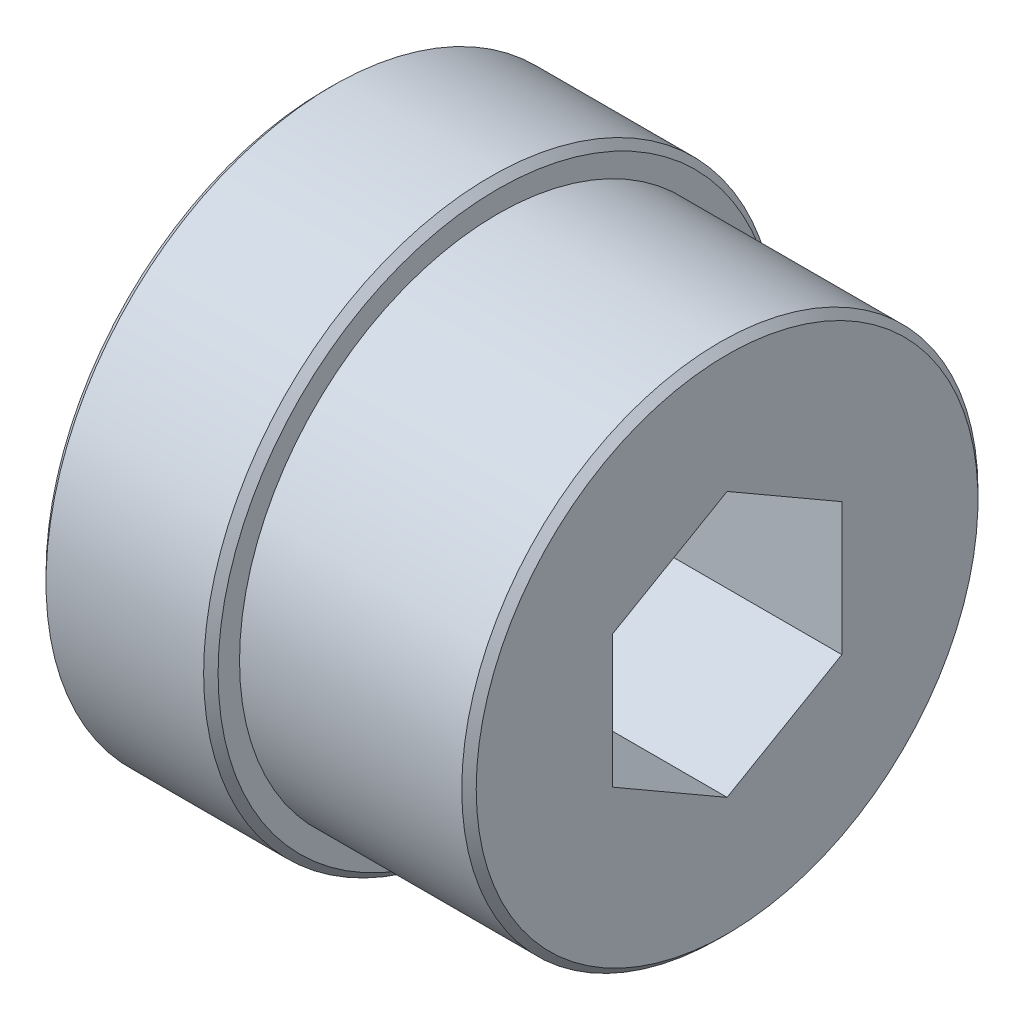
SolidWorks part; units mm, degrees
material "Nylon 101"
ref_plane "Front Plane" through (0, 0, 0) normal (0, 0, 1) x (1, 0, 0)
ref_plane "Top Plane" through (0, 0, 0) normal (0, 1, 0) x (1, 0, 0)
ref_plane "Right Plane" through (0, 0, 0) normal (1, 0, 0) x (0, 0, -1)
sketch "Sketch1" plane through (0, 0, 0) normal (1, 0, 0) x (0, 0, -1)
  circle A0 centre (0, 0) radius 14.2875
  dimension "D1" = 28.575
extrude "Boss-Extrude1" add sketch "Sketch1" along normal blind 12.7
sketch "Sketch2" plane through (0, 0, 0) normal (-1, 0, 0) x (0, 0, 1)
  circle A0 centre (0, 0) radius 15.875
  dimension "D1" = 31.75
extrude "Boss-Extrude2" add sketch "Sketch2" along normal blind 9.525
sketch "Sketch3" plane through (-9.525, 0, 0) normal (-1, 0, 0) x (0, 0, 1)
  circle A0 centre (0, 0) radius 11.1125
  dimension "D1" = 22.225
chamfer "Chamfer1" distance 0.4 angle 45 3 edges at (12.7, 0, -14.2875) (-9.525, 0, 15.875) (0, 0, 15.875)
sketch "Sketch4" plane through (-9.525, 0, 0) normal (-1, 0, 0) x (0, 0, 1)
  line L1 (0, 7.3323) -> (-6.35, 3.6662)
  line L2 (-6.35, 3.6662) -> (-6.35, -3.6662)
  line L3 (-6.35, -3.6662) -> (0, -7.3323)
  line L4 (0, -7.3323) -> (6.35, -3.6662)
  line L5 (6.35, -3.6662) -> (6.35, 3.6662)
  line L6 (6.35, 3.6662) -> (0, 7.3323)
  circle A0 centre (0, 0) radius 6.35 construction
  dimension "D1" = 12.7
extrude "Cut-Extrude1" cut sketch "Sketch4" against normal through all
